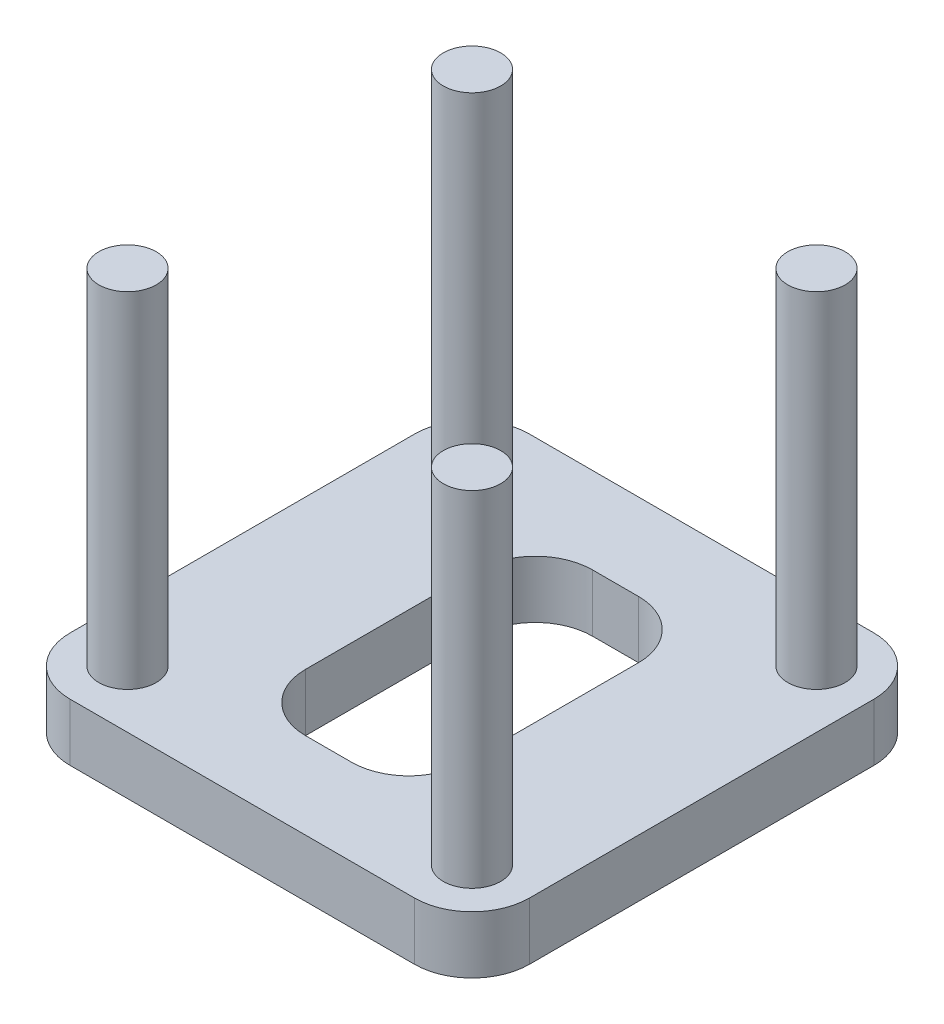
SolidWorks part; units mm, degrees
ref_plane "正面" through (0, 0, 0) normal (0, 0, 1) x (1, 0, 0)
ref_plane "平面" through (0, 0, 0) normal (0, 1, 0) x (1, 0, 0)
ref_plane "右側面" through (0, 0, 0) normal (1, 0, 0) x (0, 0, -1)
sketch "ｽｹｯﾁ1" plane through (0, 0, 0) normal (0, 1, 0) x (1, 0, 0)
  line L1 (-40, -40) -> (40, -40)
  line L2 (-40, -40) -> (-40, 40)
  line L3 (-40, 40) -> (40, 40)
  line L4 (40, -40) -> (40, 40)
  line L5 (-40, -40) -> (40, 40) construction
  line L6 (-40, 40) -> (40, -40) construction
  point P0 (0, 0)
  dimension "D1" = 80
extrude "ﾎﾞｽ - 押し出し1" add sketch "ｽｹｯﾁ1" along normal blind 10
fillet "ﾌｨﾚｯﾄ1" radius 10 4 edges at (-40, 5, -40) (40, 5, -40) (40, 5, 40) (-40, 5, 40)
sketch "ｽｹｯﾁ2" plane through (0, 0, 0) normal (0, 1, 0) x (1, 0, 0)
  line L0 (-40, 30) -> (-40, -30) construction
  line L1 (-32, 5.1) -> (-21.8, 5.1)
  line L2 (-32, 5.1) -> (-32, -5.1)
  line L3 (-32, -5.1) -> (-21.8, -5.1)
  line L4 (-21.8, 5.1) -> (-21.8, -5.1)
  line L5 (21.8, 5.1) -> (32, 5.1)
  line L6 (21.8, 5.1) -> (21.8, -5.1)
  line L7 (21.8, -5.1) -> (32, -5.1)
  line L8 (32, 5.1) -> (32, -5.1)
  line L9 (40, -30) -> (40, 30) construction
  point P8 (-21.8, 0)
  point P10 (21.8, 0)
  dimension "D1" = 8
  dimension "D2" = 10.2
  dimension "D3" = 8
extrude "ｶｯﾄ - 押し出し1" cut sketch "ｽｹｯﾁ2" along normal offset from surface (8 mm away) 2 up to face at (0, 10, 0)
sketch "ｽｹｯﾁ3" plane through (0, 10, 0) normal (0, 1, 0) x (1, 0, 0)
  line L0 (-40, 30) -> (-40, -30) construction
  line L1 (-4, -25) -> (4, -25)
  line L2 (-14, -15) -> (-14, 15)
  line L3 (-4, 25) -> (4, 25)
  line L4 (14, -15) -> (14, 15)
  line L5 (-14, -25) -> (14, 25) construction
  line L6 (-14, 25) -> (14, -25) construction
  arc A0 (4, -25) -> (14, -15) centre (4, -15) ccw
  arc A1 (-4, -25) -> (-14, -15) centre (-4, -15) cw
  arc A2 (4, 25) -> (14, 15) centre (4, 15) cw
  arc A3 (-14, 15) -> (-4, 25) centre (-4, 15) cw
  point P0 (0, 0)
  dimension "D1" = 26
  dimension "D3" = 10
  dimension "D2" = 50
extrude "ｶｯﾄ - 押し出し2" cut sketch "ｽｹｯﾁ3" against normal through all
sketch "ｽｹｯﾁ4" plane through (0, 10, 0) normal (0, 1, 0) x (1, 0, 0)
  circle A0 centre (-30, 30) radius 5
  circle A1 centre (30, 30) radius 5
  circle A2 centre (-30, -30) radius 5
  circle A3 centre (30, -30) radius 5
  arc A4 (-30, 40) -> (-40, 30) centre (-30, 30) ccw construction
  arc A5 (-40, -30) -> (-30, -40) centre (-30, -30) ccw construction
  arc A6 (30, -40) -> (40, -30) centre (30, -30) ccw construction
  arc A7 (40, 30) -> (30, 40) centre (30, 30) ccw construction
  dimension "D1" = 10
extrude "ﾎﾞｽ - 押し出し2" add sketch "ｽｹｯﾁ4" along normal blind 60
